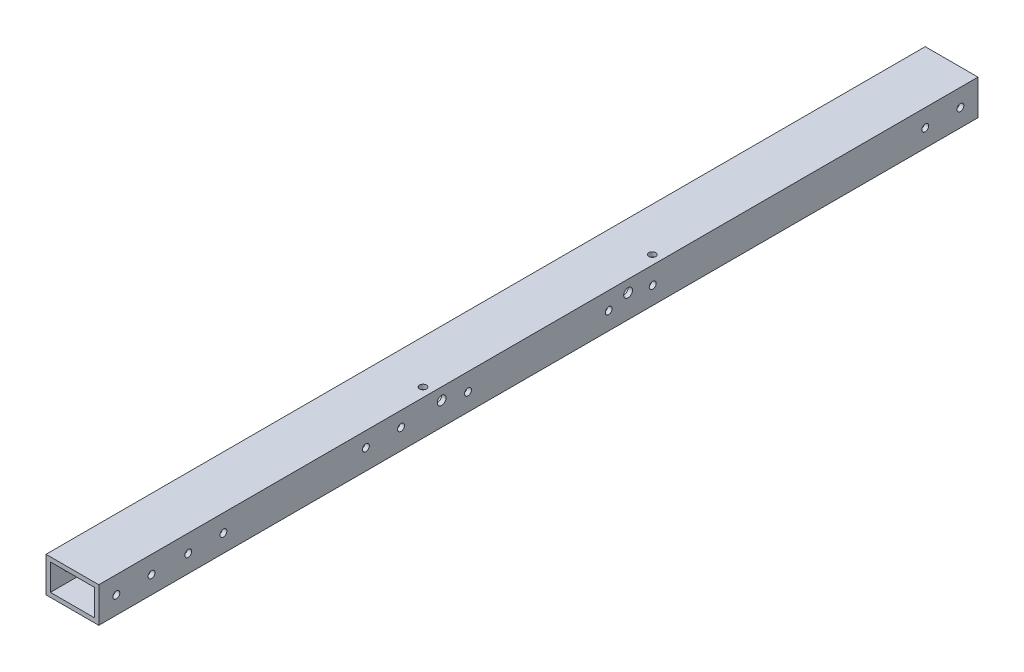
SolidWorks part; units mm, degrees
material "1060 Alloy"
ref_plane "Front Plane" through (0, 0, 0) normal (0, 0, 1) x (1, 0, 0)
ref_plane "Top Plane" through (0, 0, 0) normal (0, 1, 0) x (1, 0, 0)
ref_plane "Right Plane" through (0, 0, 0) normal (1, 0, 0) x (0, 0, -1)
sketch "Sketch1" plane through (0, 0, 0) normal (0, 0, 1) x (1, 0, 0)
  line L0 (-15.875, 9.525) -> (15.875, 9.525)
  line L2 (-19.05, 12.7) -> (19.05, 12.7)
  line L3 (-19.05, 12.7) -> (-19.05, -12.7)
  line L4 (-19.05, -12.7) -> (19.05, -12.7)
  line L5 (19.05, 12.7) -> (19.05, -12.7)
  line L10 (15.875, 9.525) -> (15.875, -9.525)
  line L11 (-15.875, -9.525) -> (15.875, -9.525)
  line L12 (-15.875, 9.525) -> (-15.875, -9.525)
  point P12 (0, 12.7)
  point P14 (19.05, 0)
  dimension "Wall Thickness" = 3.175
  dimension "Outside Width" = 38.1
  dimension "Outside Height" = 25.4
  dimension "Inside Height" = 19.05
  dimension "Inside Width" = 31.75
sketch "Sketch2" plane through (0, 0, 0) normal (1, 0, 0) x (0, 0, -1)
  line L0 (317.5, 0) -> (-317.5, 0)
  point P4 (0, 0)
  point P7 (-317.5, 0)
  point P10 (317.5, 0)
  dimension "Length" = 635
sketch "Sketch3" plane through (0, 0, 0) normal (0, 0, 1) x (1, 0, 0)
  line L21 (19.05, 12.7) -> (-19.05, 12.7)
  line L22 (19.05, -12.7) -> (19.05, 12.7)
  line L23 (-19.05, -12.7) -> (19.05, -12.7)
  line L24 (-19.05, 12.7) -> (-19.05, -12.7)
  line L25 (19.05, 12.7) -> (-19.05, 12.7)
  line L26 (19.05, -12.7) -> (19.05, 12.7)
  line L27 (-19.05, -12.7) -> (19.05, -12.7)
  line L28 (-19.05, 12.7) -> (-19.05, -12.7)
  line L29 (15.875, 9.525) -> (-15.875, 9.525)
  line L30 (15.875, -9.525) -> (15.875, 9.525)
  line L31 (-15.875, -9.525) -> (15.875, -9.525)
  line L32 (-15.875, 9.525) -> (-15.875, -9.525)
  line L33 (15.875, 9.525) -> (-15.875, 9.525)
  line L34 (15.875, -9.525) -> (15.875, 9.525)
  line L35 (-15.875, -9.525) -> (15.875, -9.525)
  line L36 (-15.875, 9.525) -> (-15.875, -9.525)
  dimension "D1" = 0
  dimension "D2" = 0
extrude "Boss-Extrude1" add sketch "Sketch3" along normal up to vertex (317.5 mm away) and the other way up to vertex (317.5 mm away) up to point (0, 0, 317.5) other way up to point (0, 0, -317.5)
sketch "Drawing Reference" plane through (0, 0, 0) normal (1, 0, 0) x (0, 0, -1)
  line L0 (-317.5, 0) -> (317.5, 0) construction
  line L1 (0, -12.7) -> (0, 12.7) construction
  line L2 (-317.5, -12.7) -> (317.5, -12.7) construction
  line L5 (-317.5, 12.7) -> (317.5, 12.7) construction
  point P7 (-290.068, 0)
  point P8 (290.068, 0)
  dimension "D1" = 27.432
sketch "Sketch4" plane through (-19.05, 0, 0) normal (-1, 0, 0) x (0, 0, 1)
  line L0 (-317.5, 0) -> (-304.8, 0)
  line L1 (-317.5, 12.7) -> (-317.5, -12.7) construction
  line L2 (-304.8, 0) -> (-279.4, 0)
  line L3 (317.5, 12.7) -> (317.5, -12.7) construction
  line L4 (317.5, 0) -> (304.8, 0)
  line L5 (304.8, 0) -> (279.4, 0)
  line L6 (0, 0) -> (50.8, 0) construction
  line L7 (0, 0) -> (-50.8, 0) construction
  point P11 (-304.8, 0)
  point P13 (-279.4, 0)
  point P14 (304.8, 0)
  point P15 (279.4, 0)
hole_wizard "#10 Clearance Hole2" positions "Sketch11" profile "Sketch12" hole size "#10" standard "ANSI Inch" end condition through all
sketch "Sketch11" plane through (-19.05, 0, 0) normal (-1, 0, 0) x (0, 0, 1)
  point P0 (-304.8, 0)
  point P3 (-279.4, 0)
  point P6 (279.4, 0)
  point P9 (304.8, 0)
sketch "Sketch12" plane through (-19.05, 0, -304.8) normal (0, 1, 0) x (0, 0, 1)
  line L0 (0, 0) -> (0, 38.1)
  line L1 (0, 38.1) -> (2.4892, 38.1)
  line L2 (2.4892, 38.1) -> (2.4892, 0)
  line L5 (2.4892, 0) -> (0, 0)
  line L11 (0, -6.35) -> (0, 107.95) construction
  dimension "Thru Hole Dia." = 4.9784
  dimension "Thru Hole Depth" = 38.1
hole_wizard "#10 Clearance Hole4" positions "Sketch14" profile "Sketch16" hole size "#10" standard "ANSI Inch" end condition through all
sketch "Sketch14" plane through (19.05, 0, 0) normal (1, 0, 0) x (0, 0, -1)
  point P33 (-252.857, 0)
  point P36 (-227.457, 0)
  point P42 (-124.587, 1.9434)
  point P45 (-99.187, 1.9434)
sketch "Sketch16" plane through (19.05, 0, 252.857) normal (0, 1, 0) x (0, 0, -1)
  line L0 (0, 0) -> (0, 38.1)
  line L1 (0, 38.1) -> (2.4892, 38.1)
  line L2 (2.4892, 38.1) -> (2.4892, 0)
  line L5 (2.4892, 0) -> (0, 0)
  line L11 (0, -6.35) -> (0, 107.95) construction
  dimension "Thru Hole Dia." = 4.9784
  dimension "Thru Hole Depth" = 38.1
hole_wizard "#10 Clearance Hole3" positions "Sketch20" profile "Sketch21" hole size "#10" standard "ANSI Inch" end condition through all
sketch "Sketch20" plane through (-19.05, 0, 0) normal (-1, 0, 0) x (0, 0, 1)
  point P0 (-50.8, 0)
  point P3 (50.8, 0)
sketch "Sketch21" plane through (-19.05, 0, -50.8) normal (0, 1, 0) x (0, 0, 1)
  line L0 (0, 0) -> (0, 38.1)
  line L1 (0, 38.1) -> (2.4892, 38.1)
  line L2 (2.4892, 38.1) -> (2.4892, 0)
  line L5 (2.4892, 0) -> (0, 0)
  line L11 (0, -6.35) -> (0, 107.95) construction
  dimension "Thru Hole Dia." = 4.9784
  dimension "Thru Hole Depth" = 38.1
sketch "Sketch22" plane through (19.05, 0, 0) normal (1, 0, 0) x (0, 0, -1)
  line L0 (50.8, 0) -> (82.55, 0) construction
hole_wizard "#10 Clearance Hole5" positions "Sketch23" profile "Sketch24" hole size "#10" standard "ANSI Inch" end condition through all
sketch "Sketch23" plane through (19.05, 0, 0) normal (1, 0, 0) x (0, 0, -1)
  point P0 (82.55, 0)
sketch "Sketch24" plane through (19.05, 0, -82.55) normal (0, 1, 0) x (0, 0, -1)
  line L0 (0, 0) -> (0, 38.1)
  line L1 (0, 38.1) -> (2.4892, 38.1)
  line L2 (2.4892, 38.1) -> (2.4892, 0)
  line L5 (2.4892, 0) -> (0, 0)
  line L11 (0, -6.35) -> (0, 107.95) construction
  dimension "Thru Hole Dia." = 4.9784
  dimension "Thru Hole Depth" = 38.1
sketch "Sketch25" plane through (0, -12.7, 0) normal (0, -1, 0) x (1, 0, 0)
  line L0 (12.4668, -88.9) -> (12.4668, 76.7543) construction
hole_wizard "#10 Clearance Hole6" positions "Sketch26" profile "Sketch27" hole size "#10" standard "ANSI Inch" end condition through all
sketch "Sketch26" plane through (0, -12.7, 0) normal (0, -1, 0) x (-1, 0, 0)
  point P0 (-12.4668, -76.7543)
  point P3 (-12.4668, 88.9)
sketch "Sketch27" plane through (12.4668, -12.7, 76.7543) normal (1, 0, 0) x (0, 0, -1)
  line L0 (0, 0) -> (0, 25.4)
  line L1 (0, 25.4) -> (2.4892, 25.4)
  line L2 (2.4892, 25.4) -> (2.4892, 0)
  line L5 (2.4892, 0) -> (0, 0)
  line L11 (0, -6.35) -> (0, 107.95) construction
  dimension "Thru Hole Dia." = 4.9784
  dimension "Thru Hole Depth" = 25.4
sketch "Sketch29" plane through (-19.05, 0, 0) normal (-1, 0, 0) x (0, 0, 1)
  line L0 (50.8, 0) -> (69.85, 0) construction
  line L1 (69.85, 0) -> (69.85, 4.2) construction
  line L2 (317.5, 12.7) -> (-317.5, 12.7) construction
  line L3 (-64.7972, 0) -> (-64.7972, 4.2) construction
  line L5 (-50.8, 0) -> (-82.55, 0) construction
  circle A0 centre (-50.8, 0) radius 6.35 construction
  circle A1 centre (-64.7972, 4.2) radius 8.25 construction
  dimension "D1" = 8.5
hole_wizard "1/4 (0.25) Diameter Hole1" positions "Sketch30" profile "Sketch31" hole size "1/4" standard "ANSI Inch" end condition through all
sketch "Sketch30" plane through (-19.05, 0, 0) normal (-1, 0, 0) x (0, 0, 1)
  point P0 (69.85, 4.2)
  point P3 (-64.7972, 4.2)
sketch "Sketch31" plane through (-19.05, 4.2, 69.85) normal (0, 1, 0) x (0, 0, 1)
  line L0 (0, 0) -> (0, 38.1)
  line L1 (0, 38.1) -> (3.175, 38.1)
  line L2 (3.175, 38.1) -> (3.175, 0)
  line L5 (3.175, 0) -> (0, 0)
  line L11 (0, -6.35) -> (0, 107.95) construction
  dimension "Thru Hole Dia." = 6.35
  dimension "Thru Hole Depth" = 38.1
equation "\"D1@Drawing Reference\"=\"Outside Width@Sketch1\" * 0.72"
